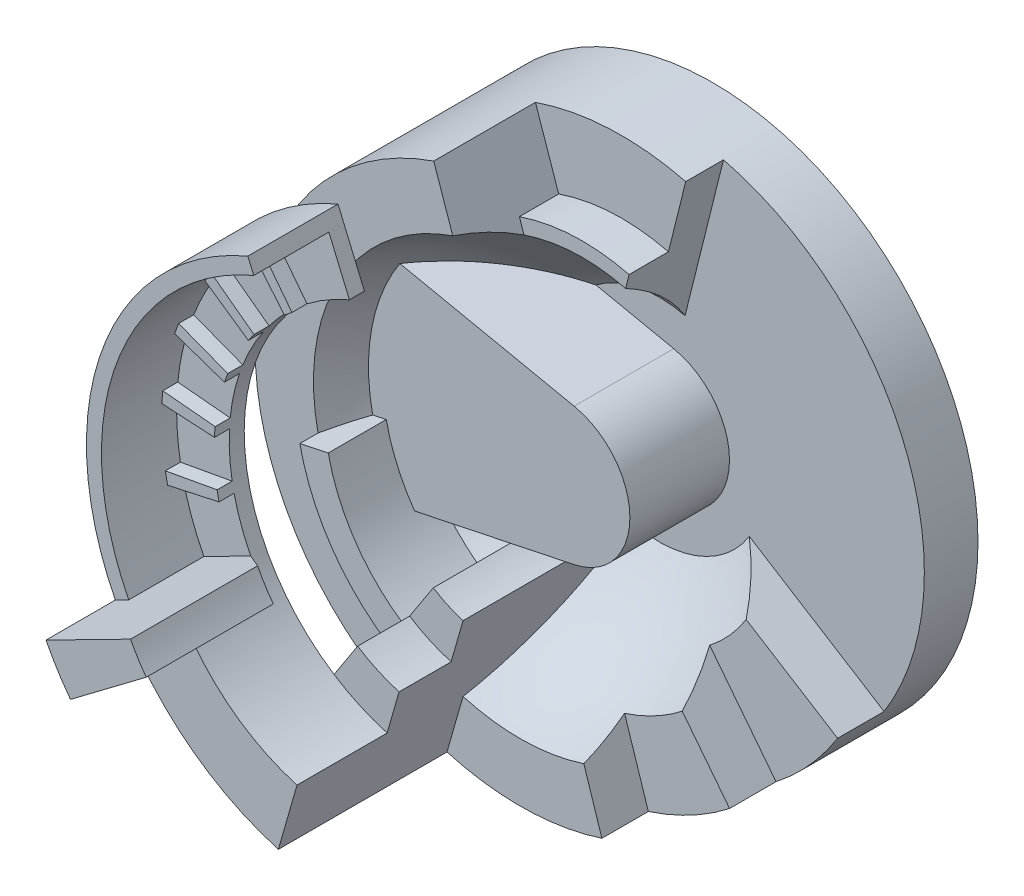
SolidWorks part; units mm, degrees
ref_plane "Front Plane" through (0, 0, 0) normal (0, 0, 1) x (1, 0, 0)
ref_plane "Top Plane" through (0, 0, 0) normal (0, 1, 0) x (1, 0, 0)
ref_plane "Right Plane" through (0, 0, 0) normal (1, 0, 0) x (0, 0, -1)
sketch "Sketch3" plane through (0, 0, 0) normal (0, 1, 0) x (1, 0, 0)
  line L0 (0, 0) -> (-5, 0) construction
  line L1 (-5, 0) -> (-5, -90)
  line L3 (0, -90) -> (0, 0) construction
  line L4 (-5, -90) -> (-36.8791, -90)
  line L8 (0, -90) -> (-5, -90) construction
  line L9 (0, -90) -> (0, -135) construction
  line L10 (0, -135) -> (0, -242) construction
  line L11 (16, -200.5) -> (16, -253.5) construction
  line L12 (0, -242) -> (107, -242) construction
  line L13 (107, -242) -> (216, -242) construction
  line L14 (0, -242) -> (0, -200.5) construction
  line L15 (232, -226) -> (200, -226)
  line L16 (232, -226) -> (232, -258)
  line L17 (232, -258) -> (200, -258)
  line L18 (200, -226) -> (200, -258)
  line L19 (232, -226) -> (200, -258) construction
  line L20 (232, -258) -> (200, -226) construction
  line L21 (16, -200.5) -> (-16, -200.5) construction
  line L22 (-16, -200.5) -> (-16, -253.5) construction
  line L23 (-16, -253.5) -> (16, -253.5) construction
  line L24 (0, -474) -> (0, -242) construction
  line L25 (-36.8791, -55) -> (-5, -55)
  line L26 (-339, -135) -> (339, -135) construction
  circle A0 centre (0, -135) radius 11.5
  circle A1 centre (0, -242) radius 11.5 construction
  circle A2 centre (107, -242) radius 11.5
  circle A8 centre (0, -242) radius 232 construction
  circle A9 centre (0, -135) radius 339 construction
  point P8 (0, -474)
  point P27 (0, -253.5)
  dimension "D3" = 23
  dimension "D9" = 53
  dimension "D1" = 45
  dimension "D2" = 107
  dimension "D4" = 107
  dimension "D5" = 109
  dimension "D6" = 32
  dimension "D7" = 35
  dimension "D8" = 32
  dimension "D10" = 32
  dimension "D12" = 10
ref_plane "Plane1" through (0, 0, 90) normal (0, 0, 1) x (1, 0, 0)
sketch "Sketch4" plane through (0, 0, 90) normal (0, 0, 1) x (1, 0, 0)
  line L0 (0, 18) -> (-40, 18)
  line L1 (18, 0) -> (-40, 0) construction
  line L2 (-36.8791, 0) -> (-5, 0) construction
  line L3 (-40, -18) -> (-40, 18)
  line L4 (0, -18) -> (-40, -18)
  line L5 (0, 0) -> (107, 0) construction
  arc A0 (0, -18) -> (0, 18) centre (0, 0) ccw
  circle A1 centre (0, 0) radius 5
  dimension "D1" = 36
  dimension "D2" = 58
extrude "Boss-Extrude1" add sketch "Sketch4" against normal up to vertex (35 mm away) contours L1 A0 L0 L3 A1 | A0 L1 A1 L3 L4 up to point (-36.8791, 0, 55)
sketch "Sketch5" plane through (0, 0, 55) normal (0, 0, -1) x (-1, 0, 0)
  line L1 (77, -55) -> (-33, -55)
  line L2 (77, -55) -> (77, 55)
  line L3 (77, 55) -> (-33, 55)
  line L4 (-33, -55) -> (-33, 55)
  line L5 (77, -55) -> (-33, 55) construction
  line L6 (77, 55) -> (-33, -55) construction
  line L7 (-18, 0) -> (-33, 0) construction
  arc A0 (0, 18) -> (0, -18) centre (0, 0) ccw construction
  arc A1 (0, 18) -> (0, -18) centre (0, 0) ccw construction
  point P0 (22, 0)
  point P7 (-18, 0)
  dimension "D1" = 110
  dimension "D2" = 110
  dimension "D3" = 15
extrude "Boss-Extrude2" add sketch "Sketch5" along normal up to vertex (55 mm away) up to point (-5, 0, 0)
sketch "Sketch7" plane through (0, 0, 0) normal (0, 0, -1) x (-1, 0, 0)
  line L4 (87, -65) -> (125, -79.9256)
  line L5 (125, -79.9256) -> (125, 79.9256)
  line L6 (232, 0) -> (-232, 0) construction
  line L7 (125, 0) -> (-43, 0) construction
  line L8 (-43, 65) -> (-43, -65)
  line L9 (-43, -65) -> (87, -65)
  line L10 (87, -65) -> (87, 65)
  line L11 (87, 65) -> (-43, 65)
  line L12 (-43, 65) -> (-43, -65)
  line L13 (-43, -65) -> (87, -65)
  line L15 (87, 65) -> (-43, 65)
  line L16 (87, 65) -> (125, 79.9256)
  dimension "D2" = 125
  dimension "D1" = 10
extrude "Boss-Extrude3" add sketch "Sketch7" against normal blind 10 contours L5 L16 L15 L12 L13 L4
fillet "Fillet1" radius 20 6 edges at (-87, 65, 5) (-125, 79.9256, 5) (43, 65, 5) (43, -65, 5) (-87, -65, 5) (-125, -79.9256, 5)
fillet "Fillet4" radius 10 14 edges at (-22, 55, 10) (-77, 0, 10) (33, 0, 10) (-77, -55, 32.5) (-22, -55, 55) (33, -55, 32.5) (-22, -55, 10) (-22, 55, 55) (-77, 0, 55) (33, 0, 55) (-40, 18, 72.5) (-40, -18, 72.5) (33, 55, 32.5) (-77, 55, 32.5)
sketch "Sketch8" plane through (0, 0, 0) normal (0, 1, 0) x (1, 0, 0)
  line L0 (0, -474) -> (0, 204)
  circle A0 centre (0, -135) radius 339 construction
  arc A1 (0, -474) -> (0, 204) centre (0, -135) ccw
revolve "Revolve1" add sketch "Sketch8" angle 360 about L0
sketch "Sketch9" plane through (0, 0, 0) normal (1, 0, 0) x (0, 0, -1)
  line L0 (0, 0) -> (0, -93.2878)
  line L1 (0, -93.2878) -> (132.5835, -93.2878)
  line L2 (132.5835, -93.2878) -> (132.5835, -141.1224)
  line L3 (0, 0) -> (204, 0)
  line L4 (204, 0) -> (204, -352.6845)
  line L5 (204, -352.6845) -> (-52.9973, -352.6845)
  line L6 (-52.9973, -352.6845) -> (-52.9973, -274.9046)
  circle A0 centre (-135, 0) radius 339 construction
  arc A2 (-52.9973, -274.9046) -> (132.5835, -141.1224) centre (-146.82, 50.8534) ccw
revolve "Revolve2" add sketch "Sketch9" angle 360 about L3
sketch "Sketch12" plane through (0, 0, 0) normal (0, 1, 0) x (1, 0, 0)
  line L0 (131.1093, -52.9973) -> (131.1093, 132.5835)
  line L1 (-274.9046, -52.9973) -> (274.9046, -52.9973) construction
  line L2 (131.1093, 132.5835) -> (352.6845, 132.5835)
  line L3 (352.6845, -52.9973) -> (352.6845, 204) construction
  line L4 (352.6845, 132.5835) -> (352.6845, -52.9973)
  line L5 (352.6845, -52.9973) -> (131.1093, -52.9973)
  line L7 (0, 0) -> (0, 204) construction
  line L8 (0, 0) -> (0, 204) construction
  point P4 (0, 132.5835)
revolve "Cut-Revolve1" cut sketch "Sketch12" angle 32 about L7
sketch "Sketch14" plane through (0, 0, 0) normal (0, 0, 1) x (1, 0, 0)
  line L1 (19.0769, -91.3164) -> (-234.0507, -144.1972)
  line L2 (-274.9046, 0) -> (0, 0) construction
  line L3 (19.0769, 91.3164) -> (-234.0507, 144.1972)
  circle A0 centre (0, 0) radius 93.2878 construction
  circle A1 centre (0, 0) radius 93.2878 construction
  arc A2 (-89.5002, 259.9274) -> (233.1323, -145.6773) centre (0, 0) ccw construction
  arc A3 (-234.0507, 144.1972) -> (-234.0507, -144.1972) centre (0, 0) ccw
  arc A4 (19.0769, -91.3164) -> (19.0769, 91.3164) centre (0, 0) ccw
extrude "Boss-Extrude4" add sketch "Sketch14" against normal up to surface (132.5835 mm away)
sketch "Sketch15" plane through (0, 0, 0) normal (0.5299, 0.848, 0) x (0.848, -0.5299, 0)
  line L0 (352.6845, 70.7232) -> (144.6583, 70.7232)
  line L1 (352.6845, -52.9973) -> (352.6845, 132.5835) construction
  line L2 (144.6583, 70.7232) -> (144.6583, -52.9973)
  line L3 (144.6583, -52.9973) -> (352.6845, -52.9973)
  line L4 (352.6845, -52.9973) -> (352.6845, 70.7232)
  line L5 (0, 0) -> (0, -190.5942) construction
  line L6 (352.6845, 70.7232) -> (352.6845, 132.5835) construction
  line L7 (274.9046, -52.9973) -> (352.6845, -52.9973) construction
  line L8 (311.8786, -52.9973) -> (311.8786, 8.8629) construction
  line L9 (311.8786, 8.8629) -> (311.8786, 70.7232) construction
revolve "Cut-Revolve2" cut sketch "Sketch15" angle 20 about L5
sketch "Sketch16" plane through (0, 0, 0) normal (0.788, 0.6157, 0) x (0, 0, -1)
  line L0 (8.8629, -352.6845) -> (8.8629, -167.4523)
  line L1 (-52.9973, -352.6845) -> (70.7232, -352.6845) construction
  line L2 (8.8629, -167.4523) -> (-94.5165, -167.4523)
  line L3 (-94.5165, -167.4523) -> (-94.5165, -352.6845)
  line L4 (-94.5165, -352.6845) -> (8.8629, -352.6845)
  line L5 (0, 0) -> (-156.3387, 0) construction
revolve "Cut-Revolve3" cut sketch "Sketch16" angle 20 about L5
sketch "Sketch17" plane through (0, 0, 0) normal (0, 1, 0) x (1, 0, 0)
  line L0 (-352.6845, -157.4422) -> (-262.6845, -157.4422)
  line L1 (-262.6845, -157.4422) -> (-262.6845, -277.4422)
  line L2 (-262.6845, -277.4422) -> (-352.6845, -277.4422)
  line L3 (-352.6845, -277.4422) -> (-352.6845, -157.4422)
  line L6 (0, 0) -> (0, -218.0807) construction
  line L7 (-352.6845, -157.4422) -> (-352.6845, -52.9973) construction
  dimension "D1" = 120
  dimension "D2" = 90
revolve "Revolve3" add sketch "Sketch17" angle 74 about L6
sketch "Sketch18" plane through (0, 0, 0) normal (0.9205, 0.3907, 0) x (0.3907, -0.9205, 0)
  line L0 (-332.6845, -277.4422) -> (-332.6845, -177.4422)
  line L1 (-352.6845, -277.4422) -> (-262.6845, -277.4422) construction
  line L2 (-332.6845, -177.4422) -> (-262.6845, -177.4422)
  line L3 (-262.6845, -277.4422) -> (-262.6845, -157.4422) construction
  line L4 (-262.6845, -177.4422) -> (-262.6845, -277.4422)
  line L5 (-262.6845, -277.4422) -> (-332.6845, -277.4422)
  line L6 (-352.6845, -157.4422) -> (-352.6845, -277.4422) construction
  line L7 (-262.6845, -157.4422) -> (-352.6845, -157.4422) construction
  line L8 (0, 0) -> (0, -177.4422) construction
  dimension "D1" = 20
  dimension "D2" = 20
revolve "Cut-Revolve4" cut sketch "Sketch18" angle 94 about L8
sketch "Sketch19" plane through (0, 0, 0) normal (0.9613, -0.2756, 0) x (0, 0, -1)
  line L0 (-157.4422, -352.6845) -> (-157.4422, -147.4009)
  line L1 (-157.4422, -262.6845) -> (-157.4422, -352.6845) construction
  line L2 (-157.4422, -147.4009) -> (149.0141, -147.4009)
  line L3 (149.0141, -147.4009) -> (149.0141, -352.6845)
  line L4 (-52.9973, -352.6845) -> (204, -352.6845) construction
  line L5 (149.0141, -352.6845) -> (-157.4422, -352.6845)
  line L6 (0, 0) -> (-127.4212, 0) construction
revolve "Revolve4" add sketch "Sketch19" angle 17 about L6
sketch "Sketch20" plane through (0, 0, 0) normal (0.9613, -0.2756, 0) x (0, 0, -1)
  line L0 (-157.4422, -147.4009) -> (-157.4422, -205.0427)
  line L1 (-157.4422, -147.4009) -> (-157.4422, -262.6845) construction
  line L2 (-157.4422, -205.0427) -> (-88.1706, -205.0427)
  line L3 (-88.1706, -205.0427) -> (-88.1706, -147.4009)
  line L4 (128.1641, -147.4009) -> (-157.4422, -147.4009) construction
  line L5 (-88.1706, -147.4009) -> (-157.4422, -147.4009)
  line L6 (0, 0) -> (-134.975, 0) construction
revolve "Cut-Revolve5" cut sketch "Sketch20" angle 360 about L6
sketch "Sketch21" plane through (0, 0, 0) normal (-0.454, 0.891, 0) x (0.891, 0.454, 0)
  line L0 (-352.6845, -177.4422) -> (-262.6845, -177.4422)
  line L1 (-262.6845, -177.4422) -> (-226.3635, -200.6355)
  line L2 (-226.3635, -200.6355) -> (-226.3635, -369.7279)
  line L3 (-226.3635, -369.7279) -> (-352.6845, -369.7279)
  line L4 (-352.6845, -369.7279) -> (-352.6845, -177.4422)
  line L7 (-352.6845, -157.4422) -> (-352.6845, -277.4422) construction
  line L8 (0, 0) -> (0, -250) construction
revolve "Revolve5" add sketch "Sketch21" angle 10 about L8
sketch "Sketch23" plane through (0, 0, 0) normal (-0.8387, 0.5446, 0) x (0, 0, 1)
  line L0 (52.9973, -274.9046) -> (77.1665, -274.9046)
  line L1 (77.1665, -274.9046) -> (77.1665, -236.2154)
  line L2 (77.1665, -236.2154) -> (-33.4922, -236.2154)
  line L3 (0, 0) -> (147.2225, 0) construction
  arc A0 (-128.1641, -147.4009) -> (52.9973, -274.9046) centre (146.82, 50.8534) ccw construction
  arc A1 (-33.4922, -236.2154) -> (52.9973, -274.9046) centre (146.82, 50.8534) ccw
revolve "Revolve6" add sketch "Sketch23" angle 45 about L3
sketch "Sketch24" plane through (0, 0, 0) normal (0.9455, 0.3256, 0) x (0, 0, -1)
  line L0 (29.948, 238.4113) -> (29.948, 257.3871)
  line L1 (29.948, 257.3871) -> (82.3252, 257.3871)
  line L2 (82.3252, 257.3871) -> (82.3252, 352.6845)
  line L3 (132.5835, 141.1224) -> (132.5835, 352.6845)
  line L4 (132.5835, 352.6845) -> (-52.9973, 352.6845)
  line L5 (-52.9973, 352.6845) -> (-52.9973, 274.9046)
  line L6 (132.5835, 141.1224) -> (132.5835, 352.6845)
  line L7 (132.5835, 352.6845) -> (82.3252, 352.6845)
  line L9 (0, 0) -> (-102.8554, 0) construction
  arc A1 (132.5835, 141.1224) -> (-52.9973, 274.9046) centre (-146.82, -50.8534) ccw
  arc A2 (132.5835, 141.1224) -> (29.948, 238.4113) centre (-146.82, -50.8534) ccw
  dimension "D1" = 0
revolve "Revolve7" add sketch "Sketch24" angle 33 about L9
delete or keep bodies "Body-Delete/Keep 1" type delete bodies bodies 104
delete or keep bodies "Body-Delete/Keep 2" type delete bodies bodies 103
sketch "Sketch25" plane through (0, 0, 177.4422) normal (0, 0, 1) x (1, 0, 0)
  line L0 (-324.5929, -72.9277) -> (-256.2079, -57.9712)
  line L1 (-326.1932, -65.3984) -> (-257.559, -51.6379) construction
  line L2 (-327.619, -57.8341) -> (-258.7537, -45.2733)
  line L3 (-314.2442, -160.1154) -> (-201.6914, -102.7669) construction
  line L4 (-314.2442, -160.1154) -> (-201.6914, -102.7669) construction
  line L5 (-102.639, 241.8023) -> (-129.9902, 306.2377) construction
  line L6 (-102.639, 241.8023) -> (-129.9902, 306.2377) construction
  line L7 (-331.4511, 24.9957) -> (-261.6388, 19.8728) construction
  line L8 (-312.3087, 113.4961) -> (-246.4184, 89.864) construction
  line L9 (-270.1644, 193.6372) -> (-213.0098, 153.2224) construction
  line L10 (-208.097, 259.5644) -> (-163.8536, 205.3194) construction
  arc A0 (-102.639, 241.8023) -> (-234.0536, -119.2563) centre (0, 0) ccw construction
  arc A1 (-129.9902, 306.2377) -> (-296.424, -151.0356) centre (0, 0) ccw construction
  arc A2 (-129.9902, 306.2377) -> (-296.424, -151.0356) centre (0, 0) ccw construction
  arc A3 (-327.619, -57.8341) -> (-324.5929, -72.9277) centre (0, 0) ccw
  arc A4 (-258.7537, -45.2733) -> (-256.2079, -57.9712) centre (0, 0) ccw
  arc A5 (-291.8761, -58.5182) -> (-265.2388, -135.1459) centre (0, 0) ccw construction
  arc A6 (-291.8761, -58.5182) -> (-296.8363, 22.4556) centre (0, 0) cw construction
  arc A7 (-185.9753, 232.4419) -> (-116.3146, 274.02) centre (0, 0) cw construction
  point P29 (2.5465, -0.9269)
  dimension "D2" = 2
  dimension "D1" = 94
  dimension "D3" = 5
extrude "Boss-Extrude5" add sketch "Sketch25" along normal blind 20
pattern_circular "CirPattern1" count 5 over 62.64 about axis through (0, 0, 0) along (0, 0, 1) of "Boss-Extrude5"
